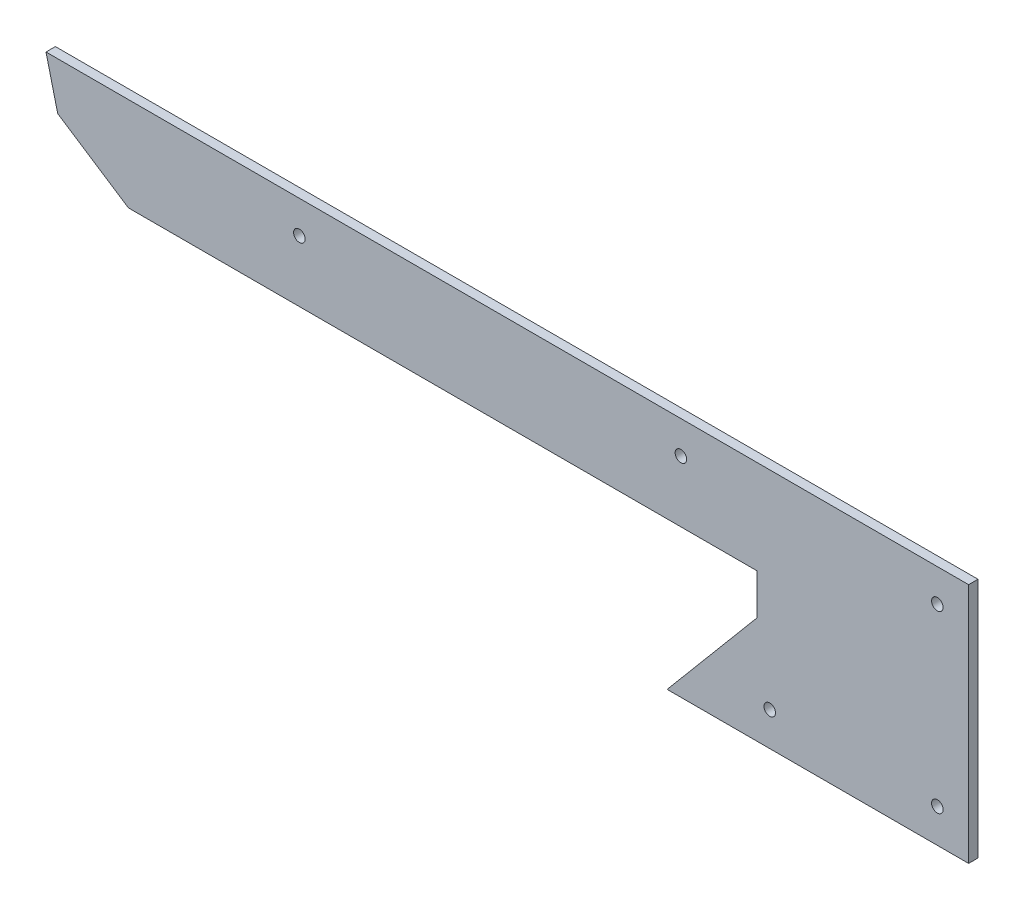
SolidWorks part; units mm, degrees
ref_plane "Ön Düzlem" through (0, 0, 0) normal (0, 0, 1) x (1, 0, 0)
ref_plane "Üst Düzlem" through (0, 0, 0) normal (0, 1, 0) x (1, 0, 0)
ref_plane "Sağ Düzlem" through (0, 0, 0) normal (1, 0, 0) x (0, 0, -1)
sketch "Çizim1" plane through (0, 0, 0) normal (0, 0, 1) x (1, 0, 0)
  line L0 (0, 0) -> (1475.0667, 0)
  line L1 (1475.0667, 0) -> (1475.0667, -386)
  line L2 (1475.0667, -386) -> (993.0667, -386)
  line L3 (993.0667, -386) -> (1136.8402, -215.0154)
  line L4 (1136.8402, -215.0154) -> (1136.8402, -150)
  line L5 (1136.8402, -150) -> (131.8402, -150)
  line L6 (131.8402, -150) -> (18.7206, -76.0154)
  line L7 (18.7206, -76.0154) -> (0, 0)
  line L8 (1774.3616, 217.9381) -> (2266.3599, 219.2262) construction
  circle A0 centre (405.0667, -52) radius 9.25
  circle A1 centre (1015.0667, -52) radius 9.25
  circle A2 centre (1425.0667, -52) radius 9.25
  circle A3 centre (1425.0667, -332) radius 9.25
  circle A4 centre (1157.0667, -332) radius 9.25
  dimension "D2" = 18.5
  dimension "D22" = 113.1196
  dimension "D3" = 52
  dimension "D4" = 610
  dimension "D5" = 410
  dimension "D6" = 52
  dimension "D7" = 50
  dimension "D8" = 1070
  dimension "D9" = 150
  dimension "D10" = 1005
  dimension "D11" = 386
  dimension "D12" = 482
  dimension "D13" = 280
  dimension "D14" = 268
  dimension "D15" = 50
  dimension "D16" = 318
  dimension "D17" = 1065.447
  dimension "D18" = 54
  dimension "D19" = 54
  dimension "D20" = 387.5874
  dimension "D21" = 313.949
  dimension "D23" = 78.2867
  dimension "D24" = 1475.0667
base flange "Taban-Flanş1" sketch "Çizim1" thickness 15 reverse thickness direction yes parameters "D1"=5
sketch "Büküm-Çizgileri1" [suppressed] plane through (0, 0, 0) normal (0, 1, 0) x (1, 0, 0)
sketch "Sınırlandırma-Kutusu1" [suppressed] plane through (0, 0, 0) normal (0, 1, 0) x (1, 0, 0)
sheet metal parameters "Sac-Levha1" thickness 15 parameters "D1"=5
flat pattern "Düz-Çoğaltma1" [suppressed]
sketch "Büküm-Çizgileri2" plane through (0, 0, 0) normal (0, 1, 0) x (1, 0, 0)
sketch3d "Sınırlandırma-Kutusu2" [suppressed]
  line L0 (0, -386, 0) -> (-1475.0667, -386, 0) construction
  line L1 (0, 0, 0) -> (-1475.0667, 0, 0) construction
  line L2 (0, -386, 0) -> (0, 0, 0) construction
  line L3 (-1475.0667, -386, 0) -> (-1475.0667, 0, 0) construction
